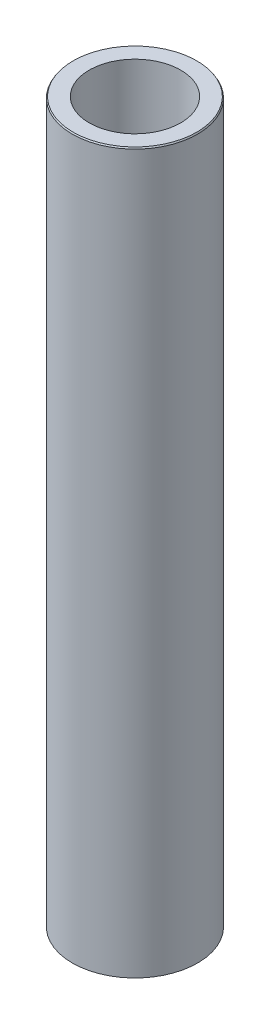
SolidWorks part; units mm, degrees
ref_plane "Front Plane" through (0, 0, 0) normal (0, 0, 1) x (1, 0, 0)
ref_plane "Top Plane" through (0, 0, 0) normal (0, 1, 0) x (1, 0, 0)
ref_plane "Right Plane" through (0, 0, 0) normal (1, 0, 0) x (0, 0, -1)
sketch "Sketch1" plane through (0, 0, 0) normal (0, 1, 0) x (1, 0, 0)
  circle A0 centre (0, 0) radius 30
  dimension "SHAFT_OD" = 60
extrude "Boss-Extrude1" add sketch "Sketch1" along normal blind 344.7991
sketch "Sketch2" plane through (0, 0, 0) normal (0, 1, 0) x (1, 0, 0)
  circle A0 centre (0, 0) radius 21.9111
  dimension "BORE_D" = 43.8222
extrude "Cut-Extrude1" cut sketch "Sketch2" along normal through all
chamfer "Chamfer1" distance 0.6367 angle 31.281 2 edges at (0, 344.7991, 30) (0, 0, 30) first distance on face at (0, 344.7991, 30) first distance on face at (0, 0, 21.9111)
